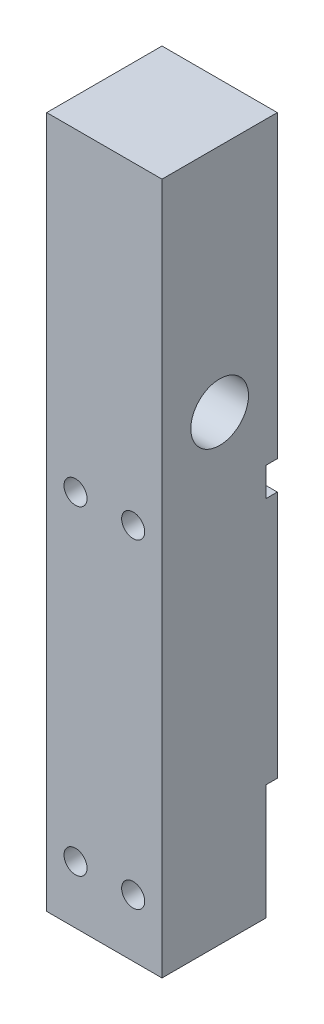
SolidWorks part; units mm, degrees
ref_plane "Front Plane" through (0, 0, 0) normal (0, 0, 1) x (1, 0, 0)
ref_plane "Top Plane" through (0, 0, 0) normal (0, 1, 0) x (1, 0, 0)
ref_plane "Right Plane" through (0, 0, 0) normal (1, 0, 0) x (0, 0, -1)
sketch "Sketch1" plane through (0, 0, 0) normal (1, 0, 0) x (0, 0, -1)
  line L0 (0, 55) -> (0, -55) construction
  line L1 (0, 120) -> (20, 120)
  line L2 (0, 120) -> (0, 0)
  line L3 (0, 0) -> (20, 0)
  line L4 (20, 120) -> (20, 0)
  line L5 (55, 0) -> (-55, 0) construction
  circle A2 centre (10, 80) radius 2.5
  dimension "D3" = 5
  dimension "D4" = 40
  dimension "D5" = 10
  dimension "D1" = 20
  dimension "D2" = 120
extrude "Boss-Extrude2" add sketch "Sketch1" against normal blind 20
ref_plane "Plane1" through (0, 0, 0) normal (1, 0, 0) x (0, 0, -1)
sketch "Sketch10" plane through (0, 0, 0) normal (1, 0, 0) x (0, 0, -1)
  circle A0 centre (10, 80) radius 5
  dimension "D1" = 10
extrude "Cut-Extrude1" cut sketch "Sketch10" against normal blind 10
ref_plane "Plane2" through (0, 0, 0) normal (0, 0, 1) x (1, 0, 0)
sketch "Sketch11" plane through (0, 0, 0) normal (0, 0, 1) x (1, 0, 0)
  line L0 (-10, 120) -> (-10, 0)
  line L1 (-20, 120) -> (0, 120) construction
  line L2 (11, 0) -> (-11, 0) construction
  line L3 (-20, 120) -> (-20, 0) construction
  line L4 (-20, 0) -> (0, 0) construction
  circle A0 centre (-15, 10) radius 1
  circle A1 centre (-5, 10) radius 1
  circle A2 centre (-15, 65.5) radius 1
  circle A3 centre (-5, 65.5) radius 1
  dimension "D1" = 2
  dimension "D4" = 2
  dimension "D2" = 5
  dimension "D3" = 10
  dimension "D5" = 65.5
extrude "Cut-Extrude2" cut sketch "Sketch11" against normal through all contours A0 | A1 | A0 region at (-15, 10, 0) region at (-5, 10, 0)
ref_plane "Plane3" through (0, 0, 0) normal (0, 0, 1) x (1, 0, 0)
sketch "Sketch12" plane through (0, 0, 0) normal (0, 0, 1) x (1, 0, 0)
  line L0 (11, 0) -> (-11, 0) construction
  circle A0 centre (-15, 10) radius 2
  circle A1 centre (-5, 10) radius 2
  circle A2 centre (-15, 65.5) radius 2
  circle A3 centre (-5, 65.5) radius 2
  dimension "D1" = 4
  dimension "D2" = 4
  dimension "D3" = 4
  dimension "D4" = 4
  dimension "D5" = 65.5
  dimension "D6" = 65.5
extrude "Cut-Extrude3" cut sketch "Sketch12" against normal blind 5
extrude "Cut-Extrude4" cut sketch "Sketch11<3>" against normal through all contours A2 | A3
sketch "Sketch11<3>" plane through (0, 0, 0) normal (0, 0, 1) x (1, 0, 0) same geometry as "Sketch11"
ref_plane "Plane4" through (0, 0, -20) normal (0, 0, -1) x (-1, 0, 0)
sketch "Sketch14" plane through (0, 0, -20) normal (0, 0, -1) x (-1, 0, 0)
  line L0 (11, 0) -> (-11, 0) construction
  line L1 (0, 68) -> (20, 68)
  line L2 (0, 68) -> (0, 63)
  line L3 (0, 63) -> (20, 63)
  line L4 (20, 68) -> (20, 63)
  line L5 (0, 68) -> (20, 63) construction
  line L6 (0, 63) -> (20, 68) construction
  line L7 (0, 20) -> (20, 20)
  line L8 (0, 20) -> (0, 0)
  line L9 (0, 0) -> (20, 0)
  line L10 (20, 20) -> (20, 0)
  line L11 (0, 20) -> (20, 0) construction
  line L12 (0, 0) -> (20, 20) construction
  line L13 (20, 0) -> (20, 120) construction
  point P0 (10, 65.5)
  point P5 (10, 10)
  dimension "D1" = 65.5
  dimension "D2" = 10
  dimension "D3" = 20
  dimension "D4" = 5
  dimension "D5" = 20
  dimension "D6" = 20
  dimension "D7" = 10
  dimension "D8" = 10
extrude "Cut-Extrude6" cut sketch "Sketch14" against normal blind 2
